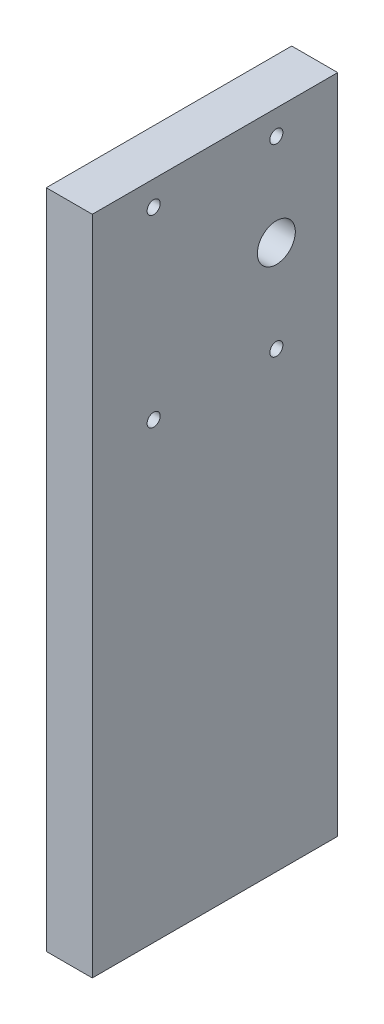
SolidWorks part; units mm, degrees
material "6061-T6 (SS)"
ref_plane "Front" through (0, 0, 0) normal (0, 0, 1) x (1, 0, 0)
ref_plane "Top" through (0, 0, 0) normal (0, 1, 0) x (1, 0, 0)
ref_plane "Right" through (0, 0, 0) normal (1, 0, 0) x (0, 0, -1)
ref_axis "side-side" through (80.9, 0, 0) along (-1, 0, 0)
ref_axis "up-down" through (0, 50, 0) along (0, -1, 0)
ref_axis "front-back" through (0, 0, -80.9) along (0, 0, 1)
sketch "Sketch1" plane through (0, 0, 0) normal (1, 0, 0) x (0, 0, -1)
  line L1 (-38.1, -91.694) -> (12.7, -91.694)
  line L2 (-38.1, -91.694) -> (-38.1, -228.6)
  line L3 (-38.1, -228.6) -> (12.7, -228.6)
  line L4 (12.7, -91.694) -> (12.7, -228.6)
  line L10 (0, -134.874) -> (-25.4, -134.874) construction
  line L11 (0, -96.774) -> (0, -134.874) construction
  line L12 (-25.4, -96.774) -> (-25.4, -134.874) construction
  line L13 (0, -96.774) -> (-25.4, -96.774) construction
  line L16 (12.7, 12.7) -> (-38.1, 12.7) construction
  circle A1 centre (0, -115.824) radius 3.925
  point P4 (31.7601, -75.9022)
  point P5 (30.9808, -85.9767)
  point P6 (0, 0)
  point P7 (0, 0)
  dimension "D1" = 5.08
  dimension "D2" = 136.906
  dimension "D3" = 241.3
extrude "Boss-Extrude1" add sketch "Sketch1" along normal mid plane 9.525
hole_wizard "#6-32 Tapped Hole1" positions "Sketch2" profile "Sketch3" tap size "#6-32" standard "ANSI Inch" end condition through all
sketch "Sketch2" plane through (4.7625, 0, 0) normal (1, 0, 0) x (0, 0, -1)
  point P0 (-25.4, -96.774)
  point P3 (0, -96.774)
  point P6 (0, -134.874)
  point P9 (-25.4, -134.874)
sketch "Sketch3" plane through (4.7625, -96.774, 25.4) normal (0, 1, 0) x (0, 0, -1)
  line L0 (0, 0) -> (0, 9.525)
  line L1 (0, 9.525) -> (1.3525, 9.525)
  line L2 (1.3525, 9.525) -> (1.3525, 0)
  line L5 (1.3525, 0) -> (0, 0)
  line L11 (0, -6.35) -> (0, 107.95) construction
  dimension "Thread Major Dia." = 2.7051
  dimension "Thru Tap Drill Depth" = 9.525
